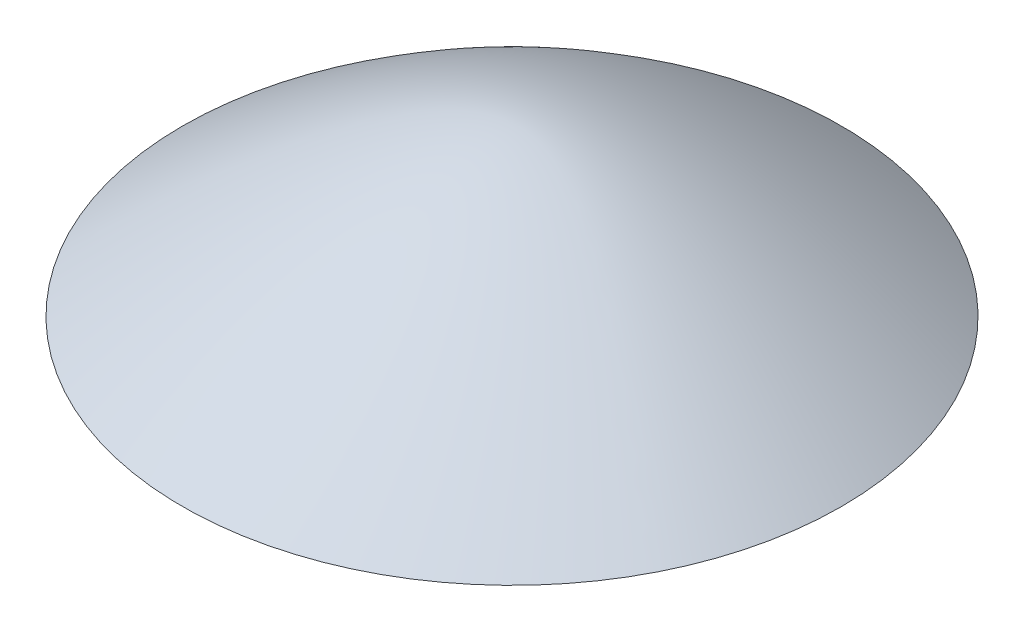
SolidWorks part; units mm, degrees
ref_plane "Front Plane" through (0, 0, 0) normal (0, 0, 1) x (1, 0, 0)
ref_plane "Top Plane" through (0, 0, 0) normal (0, 1, 0) x (1, 0, 0)
ref_plane "Right Plane" through (0, 0, 0) normal (1, 0, 0) x (0, 0, -1)
sketch "Sketch3" plane through (0, 0, 0) normal (0, 0, 1) x (1, 0, 0)
  line L2 (0, 5) -> (0, 0)
  line L4 (10, 0) -> (0, 0)
  line L5 (0, 5) -> (-1.1298, 5) construction
  line L6 (0, 4.6) -> (-1.1298, 4.6) construction
  line L7 (0.75, 0.5) -> (0.75, 4.5663)
  line L9 (0, 0) -> (2.5, 0)
  line L10 (0, 0) -> (0, 0.5)
  line L11 (0.75, 0.5) -> (2.5, 0.5)
  line L12 (2.5, 0) -> (2.5, 0.5)
  spline S0 degree 2 poles (10, 0) (3.2016, 5) (0, 5) knots 0 0 0 1 1 1
  spline S1 degree 3 poles (9.6, 0) (3.8661, 3.6923) (2.4116, 4.6) (0, 4.6) knots 0 0 0 0 1 1 1 1
  point P3 (0, 4.6)
  point P6 (9.6, 0)
  dimension "D1" = 10
  dimension "D2" = 5
  dimension "D3" = 0.4
  dimension "D4" = 0.4
  dimension "D5" = 0.75
  dimension "D6" = 0.5
  dimension "D7" = 2.5
revolve "Revolve1" add sketch "Sketch3" angle 360 about L2 region at (5.2253, 3.0218, 0) region at (0.628, 1.8802, 0)
